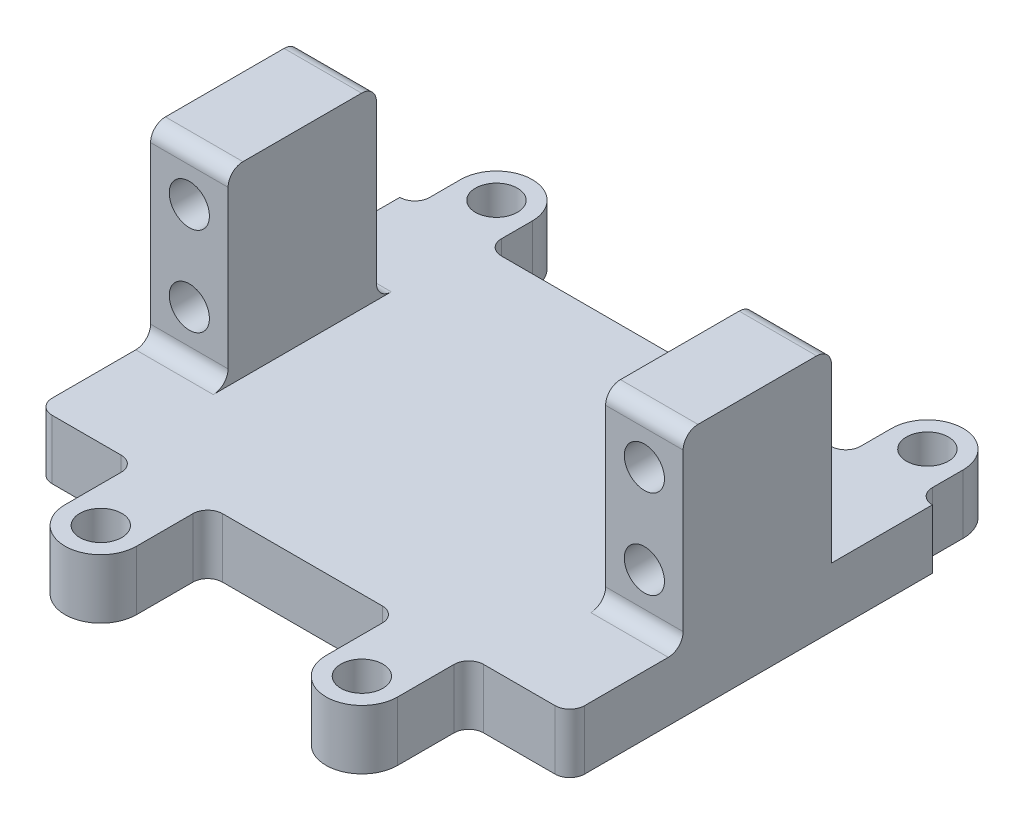
SolidWorks part; units mm, degrees
ref_plane "Front Plane" through (0, 0, 0) normal (0, 0, 1) x (1, 0, 0)
ref_plane "Top Plane" through (0, 0, 0) normal (0, 1, 0) x (1, 0, 0)
ref_plane "Right Plane" through (0, 0, 0) normal (1, 0, 0) x (0, 0, -1)
sketch "Sketch1" plane through (0, 0, 0) normal (0, 1, 0) x (1, 0, 0)
  line L1 (0, 0) -> (54.4, 0)
  line L2 (0, 0) -> (0, 38.8)
  line L3 (0, 38.8) -> (54.4, 38.8)
  line L4 (54.4, 0) -> (54.4, 38.8)
  dimension "D1" = 54.4
  dimension "D2" = 38.8
extrude "Boss-Extrude1" add sketch "Sketch1" along normal blind 3.175
sketch "Sketch2" plane through (0, 3.175, 0) normal (0, 1, 0) x (1, 0, 0)
  line L0 (0, 38.8) -> (0, 0) construction
  line L1 (0, 28) -> (7, 28)
  line L2 (0, 28) -> (0, 12.125)
  line L3 (0, 12.125) -> (7, 12.125)
  line L4 (7, 28) -> (7, 12.125)
  line L5 (54.4, 38.8) -> (0, 38.8) construction
  dimension "D1" = 15.875
  dimension "D2" = 10.8
  dimension "D3" = 7
extrude "Boss-Extrude2" add sketch "Sketch2" along normal blind 20
ref_plane "Plane1" through (27.2, 0, 0) normal (-1, 0, 0) x (0, 0, 1)
mirror "Mirror1" about plane through (27.2, 0, 0) normal (-1, 0, 0) of "Boss-Extrude2"
sketch "Sketch3" plane through (0, 3.175, 0) normal (0, 1, 0) x (1, 0, 0)
  line L0 (9.2746, -7.608) -> (9.2746, 0)
  line L1 (0, 0) -> (54.4, 0) construction
  line L2 (16.9454, -7.608) -> (16.9454, 0)
  circle A0 centre (13.11, -7.608) radius 2.2479
  circle A2 centre (13.11, -7.608) radius 3.8354
  line M12 (0, 0) -> (54.4, 0)
  dimension "D1" = 4.4958
  dimension "D4" = 1.5875
  dimension "D2" = 7.608
  dimension "D3" = 13.11
extrude "Boss-Extrude3" add sketch "Sketch3" against normal up to surface (3.175 mm away) contours A2 A0 | A2 L2 L0 M12 region at (13.11, 3.175, 2.3776) region at (13.11, 3.175, 3.8811) up to face at (27.2, 0, -19.4)
pattern_linear "LPattern1" count 2 spacing 27.94 along (1, 0, 0) of "Boss-Extrude3"
sketch "Sketch6" plane through (0, 3.175, 0) normal (0, 1, 0) x (1, 0, 0)
  line L0 (0, 38.8) -> (0, 28) construction
  line L1 (0.3048, 43.7) -> (0.3048, 38.8)
  line L2 (7.9756, 43.7) -> (7.9756, 38.8)
  line L3 (54.4, 38.8) -> (0, 38.8) construction
  circle A0 centre (4.1402, 43.7) radius 2.2479
  circle A1 centre (13.11, -7.608) radius 2.2479 construction
  circle A2 centre (4.1402, 43.7) radius 3.8354
  point P9 (0, 39.3584)
  point P10 (0.3722, 39.7404)
  point P16 (0.3722, 38.8)
  line M24 (54.4, 38.8) -> (0, 38.8)
  dimension "D2" = 4.4958
  dimension "D4" = 1.5875
  dimension "D1" = 51.308
  dimension "D3" = 4.1402
extrude "Boss-Extrude6" add sketch "Sketch6" against normal up to surface (3.175 mm away) contours A2 A0 | A2 L1 L2 M24 region at (4.1402, 3.175, -39.7736) region at (4.1402, 3.175, -47.4269) up to face at (27.12, 0, -3.2914)
mirror "Mirror3" about plane through (27.2, 0, 0) normal (-1, 0, 0) of "Boss-Extrude6"
sketch "Sketch7" plane through (0, 0, -28) normal (0, 0, -1) x (-1, 0, 0)
  line L0 (-7, 23.175) -> (-7, 3.175) construction
  line L1 (-7, 23.175) -> (0, 23.175) construction
  circle A0 centre (-2.8526, 17.925) radius 2.15
  circle A1 centre (-2.8526, 8.425) radius 2.15
  dimension "D1" = 4.3
  dimension "D2" = 4.1474
  dimension "D3" = 5.25
  dimension "D4" = 9.5
extrude "Cut-Extrude1" cut sketch "Sketch7" against normal up to surface (15.875 mm away) up to face at (3.5, 13.175, -12.125)
sketch "Sketch9" plane through (0, 0, 0) normal (-1, 0, 0) x (0, 0, 1)
  line L0 (-38.8, 0) -> (-38.8, 3.175) construction
  line L1 (-38.8, 0) -> (-38.8, 3.175)
  line L2 (-38.8, 3.175) -> (-28, 3.175)
  line L3 (-28, 3.175) -> (-28, 23.175)
  line L4 (-28, 23.175) -> (-12.125, 23.175)
  line L5 (-12.125, 23.175) -> (-12.125, 3.175)
  line L10 (0, 0) -> (-38.8, 0)
  line L11 (-12.125, 3.175) -> (0, 3.175)
  line L12 (0, 3.175) -> (0, 0)
extrude "Boss-Extrude7" add sketch "Sketch9" along normal blind 1.2948
mirror "Mirror4" about plane through (27.2, 0, 0) normal (-1, 0, 0) of "Boss-Extrude7"
mirror "Mirror5" about plane through (27.2, 0, 0) normal (-1, 0, 0) of "Cut-Extrude1"
sketch "Sketch11" plane through (0, 0, 0) normal (0, -1, 0) x (1, 0, 0)
  line L16 (55.6948, 0) -> (44.8854, 0)
  line L17 (-1.2948, 0) -> (-1.2948, -38.8)
  line L18 (-1.2948, -38.8) -> (0.3048, -38.8)
  line L19 (0.3048, -38.8) -> (0.3048, -43.7)
  line L20 (7.9756, -43.7) -> (7.9756, -38.8)
  line L21 (0.3048, -38.8) -> (0.3048, -43.7)
  line L22 (46.4244, -38.8) -> (46.4244, -43.7)
  line L23 (7.9756, -38.8) -> (46.4244, -38.8)
  line L24 (54.0952, -38.8) -> (55.6948, -38.8)
  line L25 (55.6948, -38.8) -> (55.6948, 0)
  line L26 (55.6948, 0) -> (44.8854, 0)
  line L27 (44.8854, 0) -> (44.8854, 7.608)
  line L28 (37.2146, 7.608) -> (37.2146, 0)
  line L29 (37.2146, 0) -> (16.9454, 0)
  line L30 (16.9454, 0) -> (16.9454, 7.608)
  line L31 (9.2746, 7.608) -> (9.2746, 0)
  line L33 (-1.2948, 0) -> (-1.2948, -38.8)
  line L34 (-1.2948, -38.8) -> (0.3048, -38.8)
  line L36 (7.9756, -43.7) -> (7.9756, -38.8)
  line L38 (46.4244, -38.8) -> (46.4244, -43.7)
  line L40 (54.0952, -38.8) -> (55.6948, -38.8)
  line L41 (55.6948, -38.8) -> (55.6948, 0)
  line L43 (44.8854, 0) -> (44.8854, 7.608)
  line L44 (37.2146, 7.608) -> (37.2146, 0)
  line L46 (16.9454, 0) -> (16.9454, 7.608)
  line L47 (9.2746, 7.608) -> (9.2746, 0)
  line L48 (37.2146, 0) -> (16.9454, 0)
  line L49 (9.2746, 0) -> (-1.2948, 0)
  line L50 (9.2746, 0) -> (-1.2948, 0)
  line L51 (7.9756, -38.8) -> (46.4244, -38.8)
  line L52 (54.0952, -43.7) -> (54.0952, -38.8)
  line L53 (54.0952, -43.7) -> (54.0952, -38.8)
  circle A0 centre (4.1402, -43.7) radius 2.2479 construction
  circle A1 centre (50.2598, -43.7) radius 2.2479 construction
  circle A2 centre (41.05, 7.608) radius 2.2479 construction
  circle A3 centre (13.11, 7.608) radius 2.2479 construction
  circle A4 centre (4.1402, -43.7) radius 2.2479
  circle A5 centre (50.2598, -43.7) radius 2.2479
  circle A6 centre (41.05, 7.608) radius 2.2479
  circle A7 centre (13.11, 7.608) radius 2.2479
  arc A16 (0.3048, -43.7) -> (7.9756, -43.7) centre (4.1402, -43.7) ccw
  arc A19 (46.4244, -43.7) -> (54.0952, -43.7) centre (50.2598, -43.7) ccw
  arc A23 (44.8854, 7.608) -> (37.2146, 7.608) centre (41.05, 7.608) ccw
  arc A26 (16.9454, 7.608) -> (9.2746, 7.608) centre (13.11, 7.608) ccw
  arc A30 (0.3048, -43.7) -> (7.9756, -43.7) centre (4.1402, -43.7) ccw
  arc A33 (46.4244, -43.7) -> (54.0952, -43.7) centre (50.2598, -43.7) ccw
  arc A37 (44.8854, 7.608) -> (37.2146, 7.608) centre (41.05, 7.608) ccw
  arc A40 (16.9454, 7.608) -> (9.2746, 7.608) centre (13.11, 7.608) ccw
  dimension "D1" = 0
extrude "Boss-Extrude8" add sketch "Sketch11" along normal blind 3.175
fillet "Fillet1" radius 1.5875 17 edges at (-1.2948, 0, 0) (0.3048, 0, -38.8) (7.9756, 0, -38.8) (46.4244, 0, -38.8) (54.0952, 0, -38.8) (55.6948, 0, 0) (44.8854, 0, 0) (37.2146, 0, 0) (16.9454, 0, 0) (9.2746, 0, 0) (2.8526, 23.175, -12.125) (2.8526, 3.175, -12.125) (2.8526, 3.175, -28) (2.8526, 23.175, -28) (51.5474, 3.175, -12.125) (51.5474, 23.175, -12.125) (51.5474, 23.175, -28)
